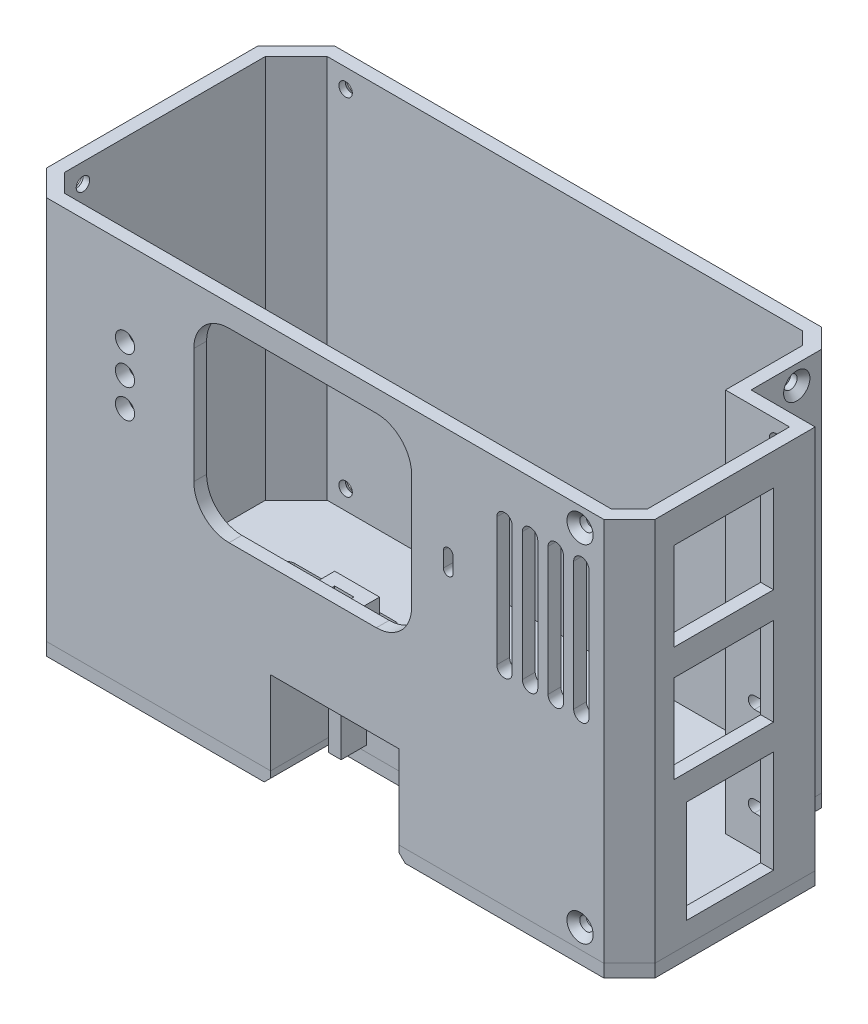
SolidWorks part; units mm, degrees
ref_plane "前视基准面" through (0, 0, 0) normal (0, 0, 1) x (1, 0, 0)
ref_plane "上视基准面" through (0, 0, 0) normal (0, 1, 0) x (1, 0, 0)
ref_plane "右视基准面" through (0, 0, 0) normal (1, 0, 0) x (0, 0, -1)
other "Configuration Table"
sketch "草图1" plane through (0, 0, 0) normal (0, 0, 1) x (1, 0, 0)
  line L1 (-105.5174, 35.9027) -> (-10.5174, 35.9027)
  line L2 (-105.5174, 35.9027) -> (-105.5174, -26.0973)
  line L3 (-105.5174, -26.0973) -> (-10.5174, -26.0973)
  line L4 (-10.5174, 35.9027) -> (-10.5174, -26.0973)
  dimension "D1" = 62
  dimension "D2" = 95
extrude "凸台-拉伸1" add sketch "草图1" along normal blind 43
sketch "草图4" plane through (0, -26.0973, 0) normal (0, -1, 0) x (1, 0, 0)
  line L0 (-10.5174, 43) -> (-10.5174, 0) construction
  line L1 (-10.5174, 14) -> (-20.5174, 14)
  line L2 (-10.5174, 14) -> (-10.5174, 0)
  line L3 (-10.5174, 0) -> (-20.5174, 0)
  line L4 (-20.5174, 14) -> (-20.5174, 0)
  line L5 (-105.5174, 0) -> (-10.5174, 0) construction
  dimension "D1" = 14
  dimension "D2" = 10
extrude "切除-拉伸3" cut sketch "草图4" against normal up to next
chamfer "倒角2" distance 6 angle 45 1 edges at (-105.5174, 4.9027, 0)
chamfer "倒角3" distance 4 angle 45 2 edges at (-105.5174, 4.9027, 43) (-10.5174, 4.9027, 43)
sketch "草图7" plane through (0, 0, 43) normal (0, 0, 1) x (1, 0, 0)
  line L0 (-101.5174, -26.0973) -> (-14.5174, -26.0973) construction
  line L1 (-46.5174, -26.0973) -> (-66.5174, -26.0973)
  line L2 (-46.5174, -26.0973) -> (-46.5174, -6.0973)
  line L3 (-46.5174, -6.0973) -> (-66.5174, -6.0973)
  line L4 (-66.5174, -26.0973) -> (-66.5174, -6.0973)
  line L6 (-10.5174, -26.0973) -> (-10.5174, 35.9027) construction
  dimension "D1" = 36
  dimension "D2" = 20
  dimension "D3" = 20
extrude "切除-拉伸5" cut sketch "草图7" against normal blind 10
shell "抽壳3" thickness 2 removed face at (-54.2952, 35.9027, 22)
sketch "草图9" plane through (0, -6.0973, 0) normal (0, -1, 0) x (1, 0, 0)
  line L0 (-44.5174, 41) -> (-68.5174, 41) construction
  line L1 (-46.5174, 41) -> (-66.5174, 41)
  line L2 (-46.5174, 41) -> (-46.5174, 33)
  line L3 (-46.5174, 33) -> (-66.5174, 33)
  line L4 (-66.5174, 41) -> (-66.5174, 33)
  line L5 (-66.5174, 33) -> (-46.5174, 33) construction
  line L8 (-66.5174, 33) -> (-66.5174, 43) construction
  line L9 (-46.5174, 33) -> (-46.5174, 43) construction
extrude "切除-拉伸6" cut sketch "草图9" against normal blind 10
sketch "草图10" plane through (0, -6.0973, 0) normal (0, -1, 0) x (1, 0, 0)
  line L4 (-66.5174, 43) -> (-66.5174, 41)
  line L5 (-66.5174, 41) -> (-46.5174, 41)
  line L6 (-46.5174, 41) -> (-46.5174, 43)
  line L7 (-46.5174, 43) -> (-66.5174, 43)
  line L8 (-66.5174, 43) -> (-66.5174, 41)
  line L9 (-66.5174, 41) -> (-46.5174, 41)
  line L10 (-46.5174, 41) -> (-46.5174, 43)
  line L11 (-46.5174, 43) -> (-66.5174, 43)
  dimension "D1" = 0
extrude "凸台-拉伸2" add sketch "草图10" along normal blind 5
sketch "草图11" plane through (0, 0, 43) normal (0, 0, 1) x (1, 0, 0)
  line L0 (-10.5174, 35.9027) -> (-10.5174, -26.0973) construction
  line L1 (-44.5174, 32.5027) -> (-78.5174, 32.5027)
  line L2 (-44.5174, 32.5027) -> (-44.5174, 3.5027)
  line L3 (-44.5174, 3.5027) -> (-78.5174, 3.5027)
  line L4 (-78.5174, 32.5027) -> (-78.5174, 3.5027)
  line L5 (-14.5174, 35.9027) -> (-101.5174, 35.9027) construction
  dimension "D1" = 34
  dimension "D2" = 29
  dimension "D3" = 34
  dimension "D4" = 3.4
extrude "切除-拉伸7" cut sketch "草图11" against normal blind 2
fillet "圆角5" radius 5.5 4 edges at (-78.5174, 32.5027, 42) (-78.5174, 3.5027, 42) (-44.5174, 32.5027, 42) (-44.5174, 3.5027, 42)
sketch "草图12" plane through (0, 0, 33) normal (0, 0, 1) x (1, 0, 0)
  line L0 (-46.5174, -4.0973) -> (-66.5174, -4.0973) construction
  line L1 (-63.5174, -4.0973) -> (-49.5174, -4.0973)
  line L2 (-63.5174, -4.0973) -> (-63.5174, -23.0973)
  line L3 (-63.5174, -23.0973) -> (-49.5174, -23.0973)
  line L4 (-49.5174, -4.0973) -> (-49.5174, -23.0973)
  line L5 (-66.5174, -4.0973) -> (-66.5174, -11.0973) construction
  line L6 (-46.5174, -4.0973) -> (-46.5174, -11.0973) construction
  line L7 (-66.5174, -26.0973) -> (-46.5174, -26.0973) construction
  dimension "D1" = 3
  dimension "D2" = 3
  dimension "D3" = 3
extrude "凸台-拉伸3" add sketch "草图12" along normal blind 4
sketch "草图13" plane through (0, -4.0973, 0) normal (0, 1, 0) x (1, 0, 0)
  line L0 (-44.5174, -31) -> (-68.5174, -31) construction
  line L1 (-61.5174, -31) -> (-51.5174, -31)
  line L2 (-61.5174, -31) -> (-61.5174, -35.5752)
  line L3 (-61.5174, -35.5752) -> (-51.5174, -35.5752)
  line L4 (-51.5174, -31) -> (-51.5174, -35.5752)
  line L5 (-68.5174, -31) -> (-68.5174, -41) construction
  line L6 (-44.5174, -31) -> (-44.5174, -41) construction
  dimension "D1" = 7
  dimension "D2" = 7
extrude "切除-拉伸8" cut sketch "草图13" against normal blind 17
sketch "草图14" plane through (0, 0, 37) normal (0, 0, 1) x (1, 0, 0)
  line L0 (-63.5174, -23.0973) -> (-49.5174, -23.0973) construction
  line L1 (-61.5174, -4.0973) -> (-51.5174, -4.0973)
  line L2 (-61.5174, -4.0973) -> (-61.5174, -23.0973)
  line L3 (-61.5174, -23.0973) -> (-51.5174, -23.0973)
  line L4 (-51.5174, -4.0973) -> (-51.5174, -23.0973)
extrude "切除-拉伸9" cut sketch "草图14" against normal up to surface (4 mm away) up to face at (-56.5174, -14.3473, 33)
chamfer "倒角4" distance 1 angle 45 2 edges at (-66.5174, -26.0973, 38) (-46.5174, -26.0973, 38)
sketch "草图15" plane through (-10.5174, 0, 0) normal (1, 0, 0) x (0, 0, -1)
  line L1 (-34.05, -4.7773) -> (-20.5, -4.7773)
  line L2 (-34.05, -4.7773) -> (-34.05, -20.7773)
  line L3 (-34.05, -20.7773) -> (-20.5, -20.7773)
  line L4 (-20.5, -4.7773) -> (-20.5, -20.7773)
  line L5 (-36, 13.0027) -> (-20.5, 13.0027)
  line L6 (-36, 13.0027) -> (-36, -0.7573)
  line L7 (-36, -0.7573) -> (-20.5, -0.7573)
  line L8 (-20.5, 13.0027) -> (-20.5, -0.7573)
  line L9 (-36, 30.9027) -> (-20.5, 30.9027)
  line L10 (-36, 30.9027) -> (-36, 17.1427)
  line L11 (-36, 17.1427) -> (-20.5, 17.1427)
  line L12 (-20.5, 30.9027) -> (-20.5, 17.1427)
extrude "切除-拉伸10" cut sketch "草图15" against normal blind 2
sketch "草图16" plane through (0, 0, 43) normal (0, 0, 1) x (1, 0, 0)
  line L0 (-38.7974, 19.2027) -> (-38.7974, 16.8027) construction
  line L1 (-38.0444, 19.2027) -> (-38.0444, 16.8027)
  line L2 (-39.5504, 19.2027) -> (-39.5504, 16.8027)
  line L3 (-44.5174, 27.0027) -> (-44.5174, 9.0027) construction
  line L5 (-44.5121, 18.0027) -> (-51.3378, 18.0027) construction
  line L6 (-10.5174, -26.0973) -> (-10.5174, 35.9027) construction
  arc A0 (-38.0444, 19.2027) -> (-39.5504, 19.2027) centre (-38.7974, 19.2027) ccw
  arc A1 (-39.5504, 16.8027) -> (-38.0444, 16.8027) centre (-38.7974, 16.8027) ccw
  point P2 (-38.7974, 18.0027)
  point P14 (-44.5174, 18.0027)
  dimension "D1" = 2.4
  dimension "D2" = 28.28
extrude "切除-拉伸11" cut sketch "草图16" against normal blind 2
sketch "草图17" plane through (0, -26.0973, 0) normal (0, -1, 0) x (1, 0, 0)
  line L0 (-105.5174, 39) -> (-105.5174, 6) construction
  line L1 (-93.9174, 13.067) -> (-84.4174, 13.067)
  line L2 (-93.9174, 13.067) -> (-93.9174, 16.567)
  line L3 (-93.9174, 16.567) -> (-84.4174, 16.567)
  line L4 (-84.4174, 13.067) -> (-84.4174, 16.567)
  line L6 (-93.9174, 20.3114) -> (-84.4174, 20.3114)
  line L7 (-93.9174, 20.3114) -> (-93.9174, 23.8114)
  line L8 (-93.9174, 23.8114) -> (-84.4174, 23.8114)
  line L9 (-84.4174, 20.3114) -> (-84.4174, 23.8114)
  line L10 (-78.1448, 23.5342) -> (-71.5448, 23.5342)
  line L11 (-78.1448, 23.5342) -> (-78.1448, 20.3114)
  line L12 (-78.1448, 20.3114) -> (-71.5448, 20.3114)
  line L13 (-71.5448, 23.5342) -> (-71.5448, 20.3114)
  line L14 (-64.6448, 23.6466) -> (-58.0448, 23.6466)
  line L15 (-64.6448, 23.6466) -> (-64.6448, 20.3114)
  line L16 (-64.6448, 20.3114) -> (-58.0448, 20.3114)
  line L17 (-58.0448, 23.6466) -> (-58.0448, 20.3114)
  line L19 (-83.4263, 17.1002) -> (-76.4263, 17.1002)
  line L20 (-83.4263, 17.1002) -> (-83.4263, 13.067)
  line L21 (-83.4263, 13.067) -> (-76.4263, 13.067)
  line L22 (-76.4263, 17.1002) -> (-76.4263, 13.067)
  line L23 (-74.9763, 17.1002) -> (-67.9763, 17.1002)
  line L24 (-74.9763, 17.1002) -> (-74.9763, 13.067)
  line L25 (-74.9763, 13.067) -> (-67.9763, 13.067)
  line L26 (-67.9763, 17.1002) -> (-67.9763, 13.067)
  line L27 (-51.5174, 16.567) -> (-43.9374, 16.567)
  line L28 (-51.5174, 16.567) -> (-51.5174, 13.767)
  line L29 (-51.5174, 13.767) -> (-43.9374, 13.767)
  line L30 (-43.9374, 16.567) -> (-43.9374, 13.767)
  line L31 (-63.5659, 16.567) -> (-52.9233, 16.567)
  line L32 (-63.5659, 16.567) -> (-63.5659, 14.767)
  line L33 (-63.5659, 14.767) -> (-52.9233, 14.767)
  line L34 (-52.9233, 16.567) -> (-52.9233, 14.767)
  dimension "D1" = 11.6
  dimension "D2" = 27.3726
  dimension "D3" = 6.9
  dimension "D4" = 6.6
  dimension "D5" = 7
  dimension "D6" = 1.45
  dimension "D7" = 9.5
  dimension "D8" = 3.5
  dimension "D9" = 2.8
  dimension "D10" = 54
  dimension "D11" = 7.58
  dimension "D12" = 1.4059
  dimension "D13" = 1.8
extrude "切除-拉伸12" cut sketch "草图17" against normal blind 2
chamfer "倒角9" distance 1 angle 45 12 edges at (-78.1448, -24.0973, 21.9228) (-74.8448, -24.0973, 23.5342) (-71.5448, -24.0973, 21.9228) (-74.8448, -24.0973, 20.3114) (-61.3448, -24.0973, 23.6466) (-64.6448, -24.0973, 21.979) (-58.0448, -24.0973, 21.979) (-61.3448, -24.0973, 20.3114) (-51.5174, -24.0973, 15.167) (-47.7274, -24.0973, 16.567) (-43.9374, -24.0973, 15.167) (-47.7274, -24.0973, 13.767)
fillet "圆角2" radius 1.2 8 edges at (-93.9174, -25.0973, 16.567) (-84.4174, -25.0973, 16.567) (-84.4174, -25.0973, 13.067) (-93.9174, -25.0973, 13.067) (-93.9174, -25.0973, 20.3114) (-93.9174, -25.0973, 23.8114) (-84.4174, -25.0973, 23.8114) (-84.4174, -25.0973, 20.3114)
fillet "圆角3" radius 0.5 18 edges at (-43.9374, -25.5973, 13.767) (-51.5174, -25.5973, 13.767) (-64.6448, -25.5973, 23.6466) (-58.0448, -25.5973, 23.6466) (-71.5448, -25.5973, 23.5342) (-78.1448, -25.5973, 23.5342) (-67.9763, -25.0973, 17.1002) (-74.9763, -25.0973, 17.1002) (-76.4263, -25.0973, 17.1002) (-83.4263, -25.0973, 17.1002) (-83.4263, -25.0973, 13.067) (-74.9763, -25.0973, 13.067) (-76.4263, -25.0973, 13.067) (-67.9763, -25.0973, 13.067) (-63.5659, -25.0973, 14.767) (-63.5659, -25.0973, 16.567) (-52.9233, -25.0973, 16.567) (-52.9233, -25.0973, 14.767)
chamfer "倒角7" distance 1 angle 45 6 edges at (-51.5174, -25.5973, 16.567) (-43.9374, -25.5973, 16.567) (-58.0448, -25.5973, 20.3114) (-64.6448, -25.5973, 20.3114) (-78.1448, -25.5973, 20.3114) (-71.5448, -25.5973, 20.3114)
sketch "草图18" plane through (0, 0, 43) normal (0, 0, 1) x (1, 0, 0)
  line L1 (-79.5174, 18.0043) -> (-81.9758, 18.0043) construction
  circle A0 centre (-89.2561, 13.5043) radius 1.5
  circle A1 centre (-89.2561, 18.0043) radius 1.5
  circle A2 centre (-89.2561, 22.5043) radius 1.5
  dimension "D3" = 3
  dimension "D2" = 3
extrude "切除-拉伸13" cut sketch "草图18" against normal blind 2
sketch "草图20" plane through (0, -24.0973, 0) normal (0, 1, 0) x (1, 0, 0)
  line L1 (-83.4263, -13.567) -> (-76.9263, -13.567)
  line L2 (-83.4263, -13.567) -> (-83.4263, -16.6002)
  line L3 (-83.4263, -16.6002) -> (-76.9263, -16.6002)
  line L4 (-76.9263, -13.567) -> (-76.9263, -16.6002)
  line L5 (-74.9763, -13.567) -> (-68.4763, -13.567)
  line L6 (-74.9763, -13.567) -> (-74.9763, -16.6002)
  line L7 (-74.9763, -16.6002) -> (-68.4763, -16.6002)
  line L8 (-68.4763, -13.567) -> (-68.4763, -16.6002)
extrude "凸台-拉伸4" add sketch "草图20" against normal blind 1
sketch "草图21" plane through (0, -25.0973, 0) normal (0, -1, 0) x (1, 0, 0)
  line L0 (-76.9263, 13.567) -> (-83.4263, 13.567) construction
  line L1 (-76.9263, 16.6002) -> (-80.9263, 16.6002)
  line L2 (-76.9263, 16.6002) -> (-76.9263, 13.567)
  line L3 (-76.9263, 13.567) -> (-80.9263, 13.567)
  line L4 (-80.9263, 16.6002) -> (-80.9263, 13.567)
  line L5 (-68.4763, 13.567) -> (-74.9763, 13.567) construction
  line L6 (-68.4763, 16.6002) -> (-72.4763, 16.6002)
  line L7 (-68.4763, 16.6002) -> (-68.4763, 13.567)
  line L8 (-68.4763, 13.567) -> (-72.4763, 13.567)
  line L9 (-72.4763, 16.6002) -> (-72.4763, 13.567)
  dimension "D1" = 4
extrude "凸台-拉伸5" add sketch "草图21" along normal up to surface (1 mm away) up to face at (-61.3448, -26.0973, 22.1299)
fillet "圆角4" radius 0.5 10 edges at (-74.9763, -25.0973, 15.0836) (-83.4263, -25.0973, 15.0836) (-80.9263, -25.5973, 13.567) (-80.9263, -25.5973, 16.6002) (-72.4763, -25.5973, 16.6002) (-72.4763, -25.5973, 13.567) (-68.4763, -25.0973, 16.6002) (-68.4763, -25.0973, 13.567) (-76.9263, -25.0973, 13.567) (-76.9263, -25.0973, 16.6002)
chamfer "倒角10" distance 2 angle 45 1 edges at (-22.5174, 5.9027, 2)
chamfer "倒角11" distance 3 angle 45 1 edges at (-20.5174, 4.9027, 0)
sketch "草图26" plane through (-20.5174, 0, 0) normal (1, 0, 0) x (0, 0, -1)
  line L0 (-10, 18.9027) -> (-10, -21.0973) construction
  line L1 (-8.6566, 18.9027) -> (-8.6566, -21.0973)
  line L2 (-11.3434, 18.9027) -> (-11.3434, -21.0973)
  line L3 (-14, -26.0973) -> (-3, -26.0973) construction
  line L5 (0, 35.9027) -> (0, -26.0973) construction
  arc A0 (-8.6566, 18.9027) -> (-11.3434, 18.9027) centre (-10, 18.9027) ccw
  arc A1 (-11.3434, -21.0973) -> (-8.6566, -21.0973) centre (-10, -21.0973) ccw
  point P2 (-10, -1.0973)
  dimension "D1" = 40
  dimension "D2" = 25
  dimension "D3" = 10
extrude "切除-拉伸15" cut sketch "草图26" against normal up to next
sketch "草图27" plane through (0, 0, 43) normal (0, 0, 1) x (1, 0, 0)
  line L1 (-18.0174, 27.9027) -> (-18.0174, 7.9027) construction
  line L8 (-16.8174, 27.9027) -> (-16.8174, 7.9027)
  line L17 (-19.2174, 27.9027) -> (-19.2174, 7.9027)
  line L25 (-14.5174, 35.9027) -> (-101.5174, 35.9027) construction
  line L28 (-10.5174, 35.9027) -> (-10.5174, -26.0973) construction
  line L31 (-22.0174, 27.9027) -> (-22.0174, 7.9027) construction
  line L34 (-20.8174, 27.9027) -> (-20.8174, 7.9027)
  line L37 (-23.2174, 27.9027) -> (-23.2174, 7.9027)
  line L38 (-26.0174, 27.9027) -> (-26.0174, 7.9027) construction
  line L39 (-24.8174, 27.9027) -> (-24.8174, 7.9027)
  line L40 (-27.2174, 27.9027) -> (-27.2174, 7.9027)
  line L41 (-30.0174, 27.9027) -> (-30.0174, 7.9027) construction
  line L42 (-28.8174, 27.9027) -> (-28.8174, 7.9027)
  line L43 (-31.2174, 27.9027) -> (-31.2174, 7.9027)
  arc A44 (-16.8174, 27.9027) -> (-19.2174, 27.9027) centre (-18.0174, 27.9027) ccw
  arc A45 (-19.2174, 7.9027) -> (-16.8174, 7.9027) centre (-18.0174, 7.9027) ccw
  arc A46 (-20.8174, 27.9027) -> (-23.2174, 27.9027) centre (-22.0174, 27.9027) ccw
  arc A47 (-23.2174, 7.9027) -> (-20.8174, 7.9027) centre (-22.0174, 7.9027) ccw
  arc A48 (-24.8174, 27.9027) -> (-27.2174, 27.9027) centre (-26.0174, 27.9027) ccw
  arc A49 (-27.2174, 7.9027) -> (-24.8174, 7.9027) centre (-26.0174, 7.9027) ccw
  arc A50 (-28.8174, 27.9027) -> (-31.2174, 27.9027) centre (-30.0174, 27.9027) ccw
  arc A51 (-31.2174, 7.9027) -> (-28.8174, 7.9027) centre (-30.0174, 7.9027) ccw
  point P2 (-18.0174, 17.9027)
  point P14 (-22.0174, 17.9027)
  point P21 (-26.0174, 17.9027)
  point P28 (-30.0174, 17.9027)
  dimension "D3" = 20
  dimension "D4" = 1.2
  dimension "D1" = 8
  dimension "D2" = 7.5
  dimension "D5" = 4
sketch "草图29" plane through (-105.5174, 0, 0) normal (-1, 0, 0) x (0, 0, 1)
  line L0 (39, -26.0973) -> (6, -26.0973) construction
  circle A0 centre (35.3017, 32.9027) radius 1.05
  circle A1 centre (35.3017, -21.0973) radius 1.2021
  dimension "D1" = 2.1
  dimension "D2" = 5
extrude "切除-拉伸18" cut sketch "草图29" against normal up to next
sketch "草图30" plane through (0, 0, 0) normal (0, 0, -1) x (-1, 0, 0)
  line L0 (99.5174, -26.0973) -> (23.5174, -26.0973) construction
  circle A0 centre (95.8191, 32.9027) radius 1.05
  circle A1 centre (95.8191, -21.0973) radius 1.05
  dimension "D1" = 2.1
  dimension "D2" = 5
extrude "切除-拉伸19" cut sketch "草图30" against normal up to next
sketch "草图31" plane through (-20.5174, 0, 0) normal (1, 0, 0) x (0, 0, -1)
  line L0 (-14, -26.0973) -> (-3, -26.0973) construction
  circle A0 centre (-6.8698, 32.9027) radius 1.05
  circle A1 centre (-6.8698, -21.0973) radius 1.05
  dimension "D1" = 2.1
  dimension "D2" = 5
extrude "切除-拉伸20" cut sketch "草图31" against normal up to next
sketch "草图32" plane through (0, 0, 14) normal (0, 0, -1) x (-1, 0, 0)
  line L0 (10.5174, -26.0973) -> (20.5174, -26.0973) construction
  circle A0 centre (14.6174, 32.9027) radius 1.05
  circle A1 centre (14.6174, -21.0973) radius 1.05
  dimension "D1" = 2.1
  dimension "D2" = 5
extrude "切除-拉伸21" cut sketch "草图32" against normal up to next
sketch "草图33" plane through (0, 0, 43) normal (0, 0, 1) x (1, 0, 0)
  line L1 (-45.5174, -26.0973) -> (-14.5174, -26.0973) construction
  circle A0 centre (-18.2157, 32.9027) radius 1.05
  circle A1 centre (-18.2157, -21.0973) radius 1.05
  dimension "D1" = 2.1
  dimension "D2" = 5
extrude "切除-拉伸22" cut sketch "草图33" against normal up to next
chamfer "倒角20" distance 1 angle 45 10 edges at (-96.8691, 32.9027, 0) (-105.5174, 31.8527, 35.3017) (-17.1657, 32.9027, 43) (-15.6674, 32.9027, 14) (-20.5174, 32.9027, 5.8198) (-17.1657, -21.0973, 43) (-15.6674, -21.0973, 14) (-96.8691, -21.0973, 0) (-105.5174, -22.2995, 35.3017) (-20.5174, -21.0973, 5.8198)
sketch "草图34" plane through (0, 0, 14) normal (0, 0, -1) x (-1, 0, 0)
  line L0 (18.0174, -4.0973) -> (14.0174, -4.0973) construction
  line L1 (18.0174, -5.0973) -> (14.0174, -5.0973)
  line L2 (18.0174, -3.0973) -> (14.0174, -3.0973)
  line L3 (18.0174, -18.0973) -> (14.0174, -18.0973) construction
  line L4 (18.0174, -19.0973) -> (14.0174, -19.0973)
  line L5 (18.0174, -17.0973) -> (14.0174, -17.0973)
  line L7 (20.5174, 35.9027) -> (20.5174, -26.0973) construction
  arc A0 (18.0174, -5.0973) -> (18.0174, -3.0973) centre (18.0174, -4.0973) ccw
  arc A1 (14.0174, -3.0973) -> (14.0174, -5.0973) centre (14.0174, -4.0973) ccw
  arc A2 (18.0174, -19.0973) -> (18.0174, -17.0973) centre (18.0174, -18.0973) ccw
  arc A3 (14.0174, -17.0973) -> (14.0174, -19.0973) centre (14.0174, -18.0973) ccw
  point P3 (16.0174, -4.0973)
  point P8 (16.0174, -18.0973)
  dimension "D1" = 1
  dimension "D2" = 4
  dimension "D3" = 2.5
  dimension "D4" = 14
extrude "切除-拉伸25" cut sketch "草图34" against normal up to next (2 mm away) draft 2
extrude "切除-拉伸26" cut sketch "草图27" against normal up to next
split "分割1" bodies to split 138 resulting bodies 139 140 split by face at (-47.7274, -24.0973, 15.167)
